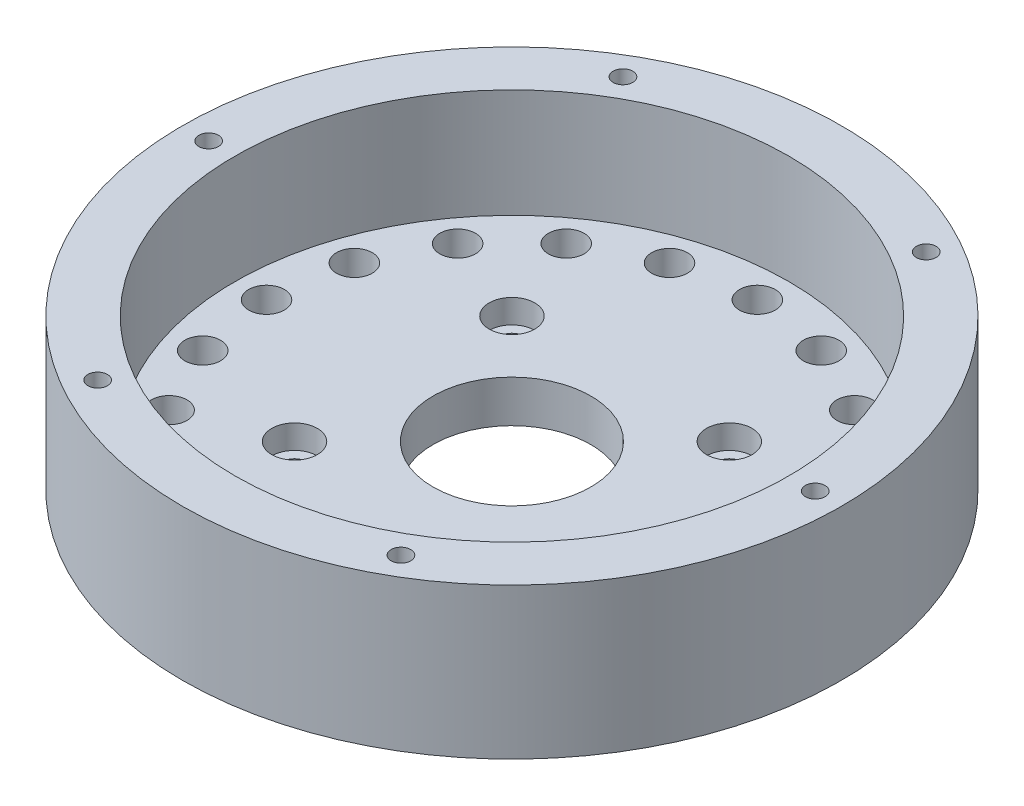
SolidWorks part; units mm, degrees
ref_plane "Front Plane" through (0, 0, 0) normal (0, 0, 1) x (1, 0, 0)
ref_plane "Top Plane" through (0, 0, 0) normal (0, 1, 0) x (1, 0, 0)
ref_plane "Right Plane" through (0, 0, 0) normal (1, 0, 0) x (0, 0, -1)
sketch "Sketch1" plane through (0, 0, 0) normal (0, 1, 0) x (1, 0, 0)
  circle A0 centre (0, 0) radius 47
  dimension "D1" = 94
extrude "Base body" add sketch "Sketch1" along normal blind 21.5
sketch "Sketch3" plane through (0, 21.5, 0) normal (0, 1, 0) x (1, 0, 0)
  circle A0 centre (0, 0) radius 39.5
  dimension "D1" = 79
extrude "Cavity" cut sketch "Sketch3" against normal blind 15.5
sketch "Sketch4" plane through (0, 6, 0) normal (0, 1, 0) x (1, 0, 0)
  circle A0 centre (0, 0) radius 11.25
  dimension "D1" = 22.5
extrude "Motor hole" cut sketch "Sketch4" against normal through all
hole_wizard "Motor screw holes" positions "Sketch5" profile "Sketch6" counterbore size "M3" standard "ISO" end condition through all
sketch "Sketch5" plane through (0, 6, 0) normal (0, 1, 0) x (1, 0, 0)
  line L1 (15.5, 15.5) -> (-15.5, 15.5) construction
  line L2 (15.5, 15.5) -> (15.5, -15.5) construction
  line L3 (15.5, -15.5) -> (-15.5, -15.5) construction
  line L4 (-15.5, 15.5) -> (-15.5, -15.5) construction
  line L5 (15.5, 15.5) -> (-15.5, -15.5) construction
  line L6 (15.5, -15.5) -> (-15.5, 15.5) construction
  point P1 (0, 0)
  point P2 (-15.5, -15.5)
  point P955 (15.5, 15.5)
  point P956 (15.5, -15.5)
  point P957 (-15.5, 15.5)
  dimension "D1" = 31
  dimension "D2" = 31
sketch "Sketch6" plane through (0, 6, 0) normal (1, 0, 0) x (0, 0, 1)
  line L0 (0, 0) -> (0, 6)
  line L1 (0, 6) -> (1.8, 6)
  line L3 (1.8, 6) -> (1.8, 3.4)
  line L4 (1.8, 3.4) -> (3.25, 3.4)
  line L5 (3.25, 3.4) -> (3.25, 0)
  line L7 (3.25, 0) -> (0, 0)
  line L11 (0, -6.35) -> (0, 107.95) construction
  dimension "Thru Hole Dia." = 3.6
  dimension "Thru Hole Depth" = 6
  dimension "C'Bore Dia." = 6.5
  dimension "C'Bore Depth" = 3.4
sketch "Sketch8" plane through (0, 6, 0) normal (0, 1, 0) x (1, 0, 0)
  circle A0 centre (-35, 0) radius 2.55
  circle A1 centre (-33.287, 10.8156) radius 2.55
  circle A2 centre (-28.3156, 20.5725) radius 2.55
  circle A3 centre (-20.5725, 28.3156) radius 2.55
  circle A4 centre (-10.8156, 33.287) radius 2.55
  circle A5 centre (0, 35) radius 2.55
  circle A6 centre (10.8156, 33.287) radius 2.55
  circle A7 centre (20.5725, 28.3156) radius 2.55
  circle A8 centre (28.3156, 20.5725) radius 2.55
  circle A9 centre (33.287, 10.8156) radius 2.55
  circle A10 centre (35, 0) radius 2.55
  circle A11 centre (33.287, -10.8156) radius 2.55
  circle A12 centre (28.3156, -20.5725) radius 2.55
  circle A13 centre (20.5725, -28.3156) radius 2.55
  circle A14 centre (10.8156, -33.287) radius 2.55
  circle A15 centre (0, -35) radius 2.55
  circle A16 centre (-10.8156, -33.287) radius 2.55
  circle A17 centre (-20.5725, -28.3156) radius 2.55
  circle A18 centre (-28.3156, -20.5725) radius 2.55
  circle A19 centre (-33.287, -10.8156) radius 2.55
  point P44 (0, 0)
  dimension "D1" = 5.1
  dimension "D2" = 35
  dimension "D3" = 20
extrude "Ring pin holes" cut sketch "Sketch8" against normal blind 5
sketch "Sketch9" plane through (0, 21.5, 0) normal (0, 1, 0) x (1, 0, 0)
  circle A0 centre (-43.25, 0) radius 1.4
  circle A1 centre (-21.625, 37.4556) radius 1.4
  circle A2 centre (21.625, 37.4556) radius 1.4
  circle A3 centre (43.25, 0) radius 1.4
  circle A4 centre (21.625, -37.4556) radius 1.4
  circle A5 centre (-21.625, -37.4556) radius 1.4
  point P16 (0, 0)
  dimension "D1" = 2.8
  dimension "D2" = 43.25
  dimension "D3" = 6
extrude "Cap screw holes" cut sketch "Sketch9" against normal blind 10
